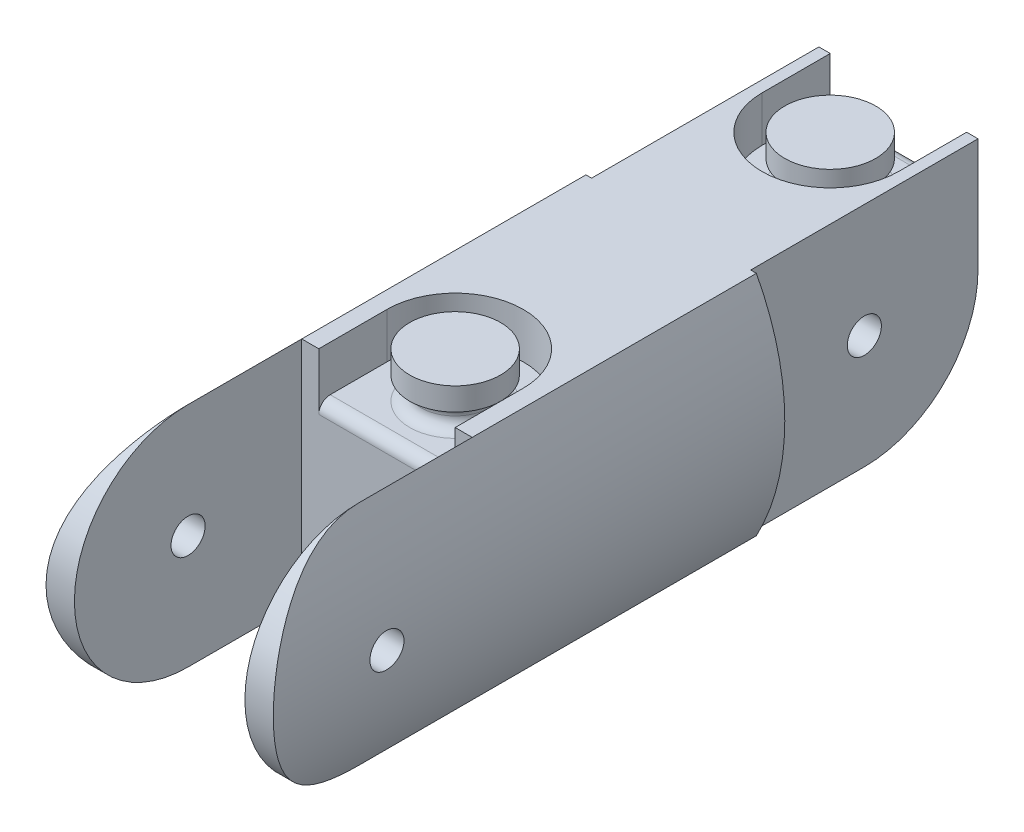
SolidWorks part; units mm, degrees
ref_plane "Alzado" through (0, 0, 0) normal (0, 0, 1) x (1, 0, 0)
ref_plane "Planta" through (0, 0, 0) normal (0, 1, 0) x (1, 0, 0)
ref_plane "Vista lateral" through (0, 0, 0) normal (1, 0, 0) x (0, 0, -1)
sketch "Croquis2" plane through (0, 0, 0) normal (0, 0, 1) x (1, 0, 0)
  line L5 (-7.5, -10) -> (7.5, -10)
  line L7 (-7.5, 10) -> (7.5, 10)
  line L9 (-7.5, -10) -> (7.5, 10) construction
  line L10 (-7.5, 10) -> (7.5, -10) construction
  arc A2 (-7.5, 10) -> (-7.5, -10) centre (11.25, 0) ccw
  arc A3 (7.5, -10) -> (7.5, 10) centre (-11.25, 0) ccw
  point P0 (0, 0)
  dimension "D1" = 15
  dimension "D2" = 20
extrude "Saliente-Extruir2" add sketch "Croquis2" along normal blind 45
sketch "Croquis4" plane through (0, 0, 0) normal (0, 0, -1) x (-1, 0, 0)
  line L1 (7.5, -10) -> (-7.5, -10) construction
  circle A0 centre (0, -7) radius 1.5
  dimension "D2" = 3
  dimension "D1" = 3
extrude "Cortar-Extruir1" cut sketch "Croquis4" against normal blind 50
sketch "Croquis3" plane through (0, 0, 0) normal (0, 0, -1) x (-1, 0, 0)
  line L8 (7.5, -10) -> (-7.5, -10) construction
  line L10 (7, 10) -> (7, -10)
  line L11 (7, -10) -> (3, -10)
  line L12 (-7, 10) -> (-7, -10)
  line L13 (7, 10) -> (-7, -10) construction
  line L14 (7, -10) -> (-7, 10) construction
  line L16 (3, -3) -> (3, -10)
  line L17 (-3, -10) -> (-7, -10)
  line L19 (-3, -3) -> (3, -3)
  line L20 (-3, -3) -> (-3, -10)
  line L21 (-7, 10) -> (7, 10)
  point P0 (0, 0)
  dimension "D1" = 14
  dimension "D2" = 4
  dimension "D3" = 4
  dimension "D4" = 7
extrude "Saliente-Extruir3" add sketch "Croquis3" along normal blind 20
sketch "Croquis8" plane through (-7, 0, 0) normal (-1, 0, 0) x (0, 0, 1)
  line L0 (-20, -10) -> (-20, 10) construction
  line L1 (-20, -10) -> (0, -10) construction
  circle A0 centre (-10, 0) radius 1.5
  point P4 (-20, 0)
  dimension "D1" = 3
  dimension "D2" = 10
  dimension "D3" = 10
extrude "Cortar-Extruir4" cut sketch "Croquis8" against normal blind 14
fillet "Redondeo1" radius 10 2 edges at (-5, -10, -20) (5, -10, -20)
sketch "Croquis6" plane through (0, 0, 45) normal (0, 0, 1) x (1, 0, 0)
  line L1 (-7.5, 10) -> (7.5, 10)
  line L2 (-7.5, 10) -> (-7.5, -10)
  line L3 (-7.5, -10) -> (7.5, -10)
  line L4 (7.5, 10) -> (7.5, -10)
extrude "Cortar-Extruir2" cut sketch "Croquis6" against normal blind 20
sketch "Croquis7" plane through (0, 0, 0) normal (1, 0, 0) x (0, 0, -1)
  line L0 (-45, 10) -> (-45, -10) construction
  line L2 (-35, -10) -> (-50, -10)
  line L4 (-35, 10) -> (-50, 10)
  line L5 (-50, -10) -> (-50, 10)
  arc A0 (-35, 10) -> (-35, -10) centre (-35, 0) ccw
  circle A1 centre (-35, 0) radius 1.5
  dimension "D3" = 10
  dimension "D4" = 3
  dimension "D1" = 10
  dimension "D2" = 15
  dimension "D5" = 20
extrude "Cortar-Extruir3" cut sketch "Croquis7" against normal through all both and the other way through all
sketch "Sketch1" plane through (0, 10, 0) normal (0, 1, 0) x (1, 0, 0)
  line L0 (-7, 20) -> (7, 20) construction
  line L1 (7.5, -25) -> (-7.5, -25) construction
  line L4 (-6, 14) -> (-6, 20)
  line L5 (-6, 20) -> (6, 20)
  line L6 (6, 14) -> (6, 20)
  line L8 (-6, -19) -> (-6, -25)
  line L9 (-6, -25) -> (6, -25)
  line L10 (6, -19) -> (6, -25)
  arc A0 (6, -19) -> (-6, -19) centre (0, -19) ccw
  arc A1 (-6, 14) -> (6, 14) centre (0, 14) ccw
  dimension "D3" = 12
  dimension "D4" = 12
  dimension "D1" = 6
  dimension "D2" = 6
extrude "Cut-Extrude1" cut sketch "Sketch1" against normal blind 4
sketch "Sketch2" plane through (0, 6, 0) normal (0, 1, 0) x (1, 0, 0)
  circle A0 centre (0, -19) radius 3
  circle A1 centre (0, 14) radius 3
  dimension "D1" = 6
  dimension "D2" = 6
extrude "Boss-Extrude1" add sketch "Sketch2" along normal blind 2
sketch "Sketch3" plane through (0, 8, 0) normal (0, 1, 0) x (1, 0, 0)
  circle A0 centre (0, -19) radius 4
  circle A1 centre (0, 14) radius 4
  dimension "D1" = 8
  dimension "D2" = 8
extrude "Boss-Extrude2" add sketch "Sketch3" along normal blind 2
fillet "Fillet2" radius 1 4 edges at (0, 8, -11) (0, 6, -11) (0, 8, 22) (0, 6, 22)
fillet "Fillet3" radius 1 2 edges at (0, 6, -20) (0, 6, 25)
fillet "Fillet4" radius 1 2 edges at (-1.5, -7, 0) (1.5, -7, 25)
